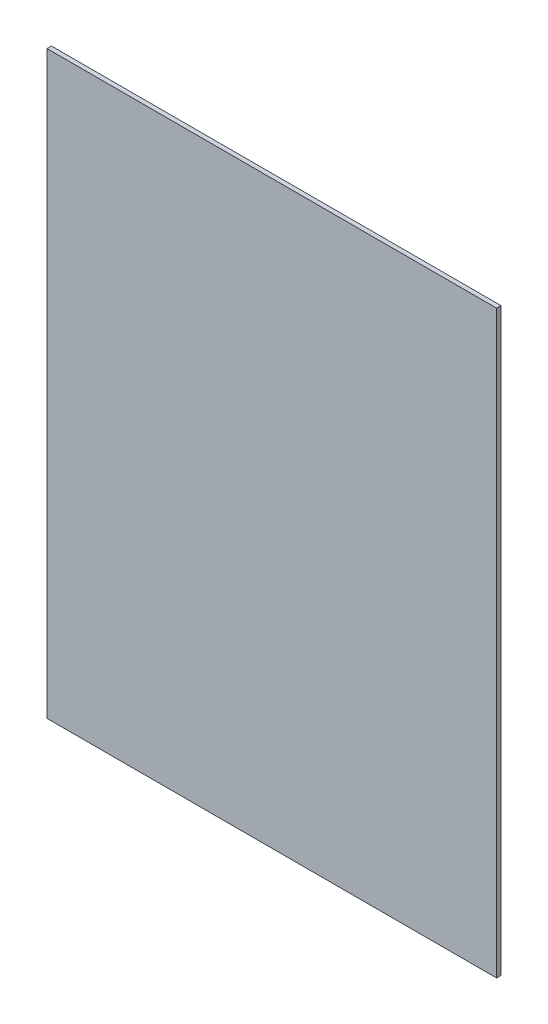
SolidWorks part; units mm, degrees
ref_plane "Front Plane" through (0, 0, 0) normal (0, 0, 1) x (1, 0, 0)
ref_plane "Top Plane" through (0, 0, 0) normal (0, 1, 0) x (1, 0, 0)
ref_plane "Right Plane" through (0, 0, 0) normal (1, 0, 0) x (0, 0, -1)
sketch "Sketch1" plane through (0, 0, 0) normal (0, 0, 1) x (1, 0, 0)
  line L1 (0, 0) -> (155, 0)
  line L2 (0, 0) -> (0, 200)
  line L3 (0, 200) -> (155, 200)
  line L4 (155, 0) -> (155, 200)
  dimension "D1" = 200
  dimension "D2" = 155
extrude "Bottom Outer Casing" add sketch "Sketch1" along normal blind 1.5189
